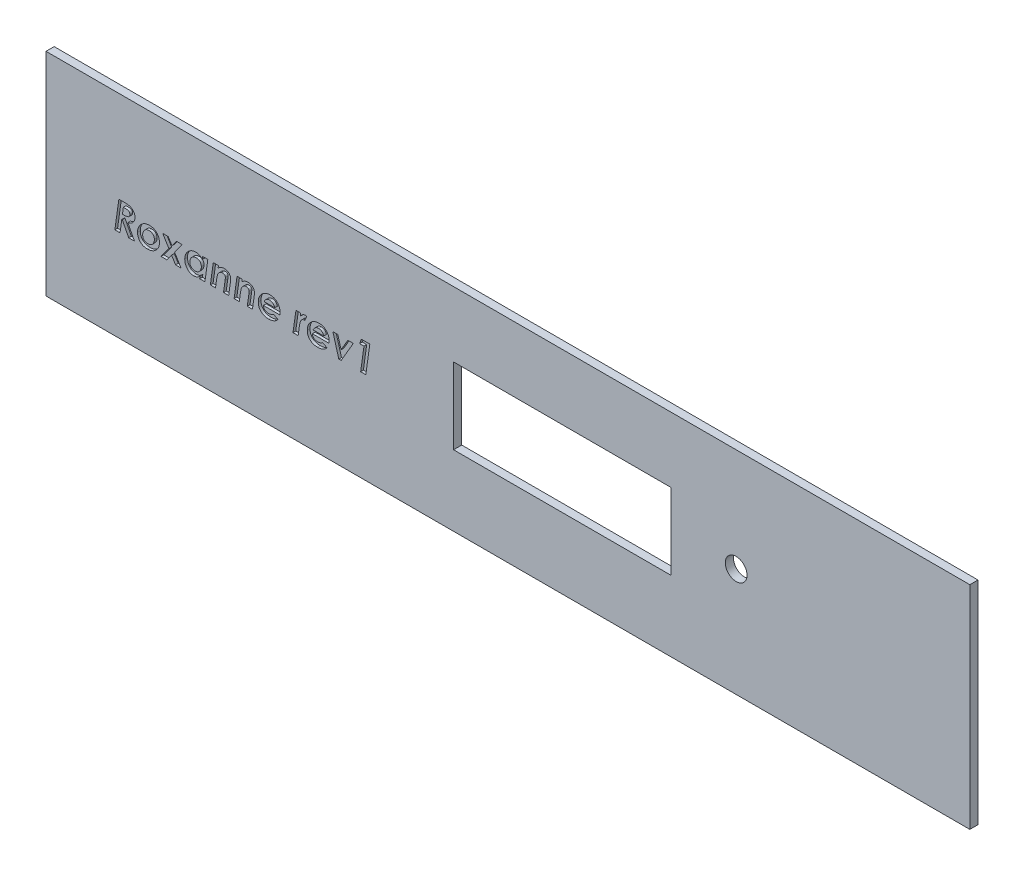
SolidWorks part; units mm, degrees
ref_plane "Plan de face" through (0, 0, 0) normal (0, 0, 1) x (1, 0, 0)
ref_plane "Plan de dessus" through (0, 0, 0) normal (0, 1, 0) x (1, 0, 0)
ref_plane "Plan de droite" through (0, 0, 0) normal (1, 0, 0) x (0, 0, -1)
sketch "Esquisse1" plane through (0, 0, 0) normal (0, 0, 1) x (1, 0, 0)
  line L1 (-170, 39) -> (170, 39)
  line L2 (-170, 39) -> (-170, -39)
  line L3 (-170, -39) -> (170, -39)
  line L4 (170, 39) -> (170, -39)
  dimension "D1" = 340
  dimension "D2" = 170
  dimension "D3" = 78
  dimension "D4" = 39
extrude "Boss.-Extru.1" add sketch "Esquisse1" along normal blind 3
sketch "Esquisse3" plane through (0, 0, 3) normal (0, 0, 1) x (1, 0, 0)
  text T0 "<b><i>Roxanne rev1</i></b>" font "Century Gothic" height 10.5
extrude "Enlèv. mat.-Extru.2" cut sketch "Esquisse3" against normal blind 1
sketch "Esquisse4" plane through (0, 0, 3) normal (0, 0, 1) x (1, 0, 0)
  line L0 (170, 39) -> (-170, 39) construction
  line L1 (-20, 15) -> (60, 15)
  line L2 (-20, 15) -> (-20, -13)
  line L3 (-20, -13) -> (60, -13)
  line L4 (60, 15) -> (60, -13)
  line L5 (-170, 39) -> (-170, -39) construction
  circle A0 centre (84, 1) radius 4
  dimension "D5" = 8
  dimension "D1" = 28
  dimension "D2" = 80
  dimension "D3" = 24
  dimension "D4" = 150
  dimension "D6" = 24
  dimension "D7" = 14
extrude "Enlèv. mat.-Extru.3" cut sketch "Esquisse4" against normal through all
